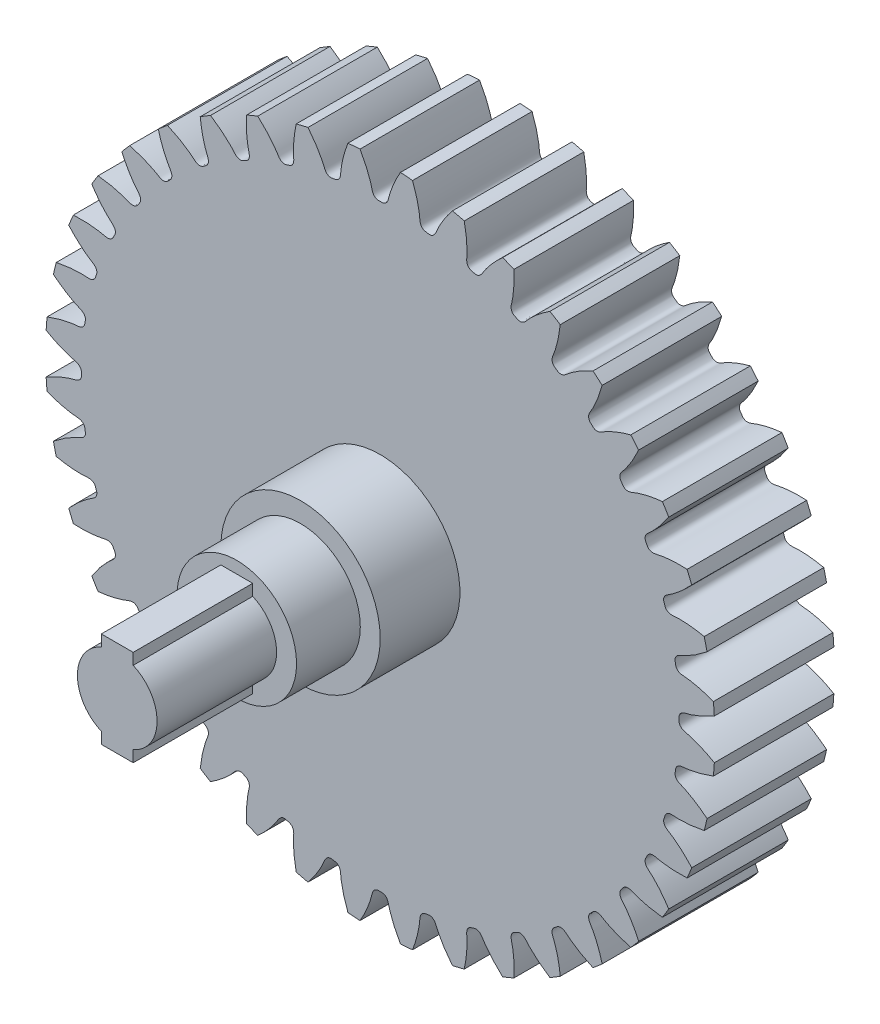
SolidWorks part; units mm, degrees
ref_plane "Front Plane" through (0, 0, 0) normal (0, 0, 1) x (1, 0, 0)
ref_plane "Top Plane" through (0, 0, 0) normal (0, 1, 0) x (1, 0, 0)
ref_plane "Right Plane" through (0, 0, 0) normal (1, 0, 0) x (0, 0, -1)
ref_axis "Axis1" through (0, 0, 55) along (0, 0, -1)
sketch "旋转草图小直齿轮" plane through (0, 0, 0) normal (1, 0, 0) x (0, 0, -1)
  line L0 (0, 0) -> (1, 0) construction
  line L1 (-7.5, 0) -> (-7.5, 42)
  line L2 (-7.5, 42) -> (7.5, 42)
  line L3 (7.5, 42) -> (7.5, 0)
  line L4 (7.5, 0) -> (-7.5, 0)
  dimension "Side1" = 7.5
  dimension "OutsideRadius" = 42
  dimension "Side2" = 7.5
revolve "小直齿轮" add sketch "旋转草图小直齿轮" angle 360 about L0
sketch "齿草图小直齿轮" plane through (0, 0, 0) normal (0, 0, 1) x (1, 0, 0)
  arc A0 (42.0201, 2.5926) -> (42.0201, -2.5926) centre (0, 0) cw
  spline S0 degree 3 poles (42.0201, -2.5926) (41.745, -2.4319) (41.3797, -2.2305) (40.9231, -2.0003) (40.668, -1.8774) (40.4215, -1.7639) (40.1839, -1.6595) (39.9554, -1.564) (39.7362, -1.4769) (39.5266, -1.3979) (39.3268, -1.3265) (39.1369, -1.2625) (38.9572, -1.2055) (38.7879, -1.155) (38.629, -1.1109) (38.4345, -1.0595) (38.2747, -1.0262) (38.152, -0.9881) (38.1049, -0.9719) (38.0584, -0.9542) (38.0124, -0.9347) (37.9666, -0.9132) (37.9208, -0.8892) (37.8747, -0.8622) (37.8283, -0.8314) (37.7813, -0.796) (37.7338, -0.7549) (37.6862, -0.7065) (37.6393, -0.6494) (37.5946, -0.5822) (37.5547, -0.5038) (37.523, -0.4143) (37.5038, -0.3202) (37.496, -0.1809) (37.5029, 0) (37.496, 0.1809) (37.5038, 0.3202) (37.523, 0.4143) (37.5547, 0.5038) (37.5946, 0.5822) (37.6393, 0.6494) (37.6862, 0.7065) (37.7338, 0.7549) (37.7813, 0.796) (37.8283, 0.8314) (37.8747, 0.8622) (37.9208, 0.8892) (37.9666, 0.9132) (38.0124, 0.9347) (38.0584, 0.9542) (38.1049, 0.9719) (38.152, 0.9881) (38.2747, 1.0262) (38.4345, 1.0595) (38.629, 1.1109) (38.7879, 1.155) (38.9572, 1.2055) (39.1369, 1.2625) (39.3268, 1.3265) (39.5266, 1.3979) (39.7362, 1.4769) (39.9554, 1.564) (40.1839, 1.6595) (40.4215, 1.7639) (40.668, 1.8774) (40.9231, 2.0003) (41.3797, 2.2305) (41.745, 2.4319) (42.0201, 2.5926) knots 0 0 0 0 0.086797 0.113582 0.139293 0.16393 0.187494 0.209983 0.231398 0.251739 0.271005 0.289198 0.306317 0.322362 0.337333 0.35123 0.377176 0.381719 0.386231 0.390736 0.395262 0.399843 0.40452 0.409344 0.414375 0.419685 0.425355 0.431479 0.438151 0.445453 0.45343 0.462059 0.471223 0.479506 0.5 0.520494 0.528777 0.537941 0.54657 0.554547 0.561849 0.568521 0.574645 0.580315 0.585625 0.590656 0.59548 0.600157 0.604738 0.609264 0.613769 0.618281 0.622824 0.64877 0.662667 0.677638 0.693683 0.710802 0.728995 0.748261 0.768602 0.790017 0.812506 0.83607 0.860707 0.886418 0.913203 1 1 1 1
extrude "齿拉伸切除小直齿轮" cut sketch "齿草图小直齿轮" against normal blind 7.5 and the other way blind 7.5
pattern_circular "齿形小直齿轮" count 40 every 9 about axis through (0, 0, 55) along (0, 0, -1) of "齿拉伸切除小直齿轮"
sketch "辅助草图小直齿轮" plane through (0, 0, 0) normal (0, 0, 1) x (1, 0, 0)
  circle A0 centre (0, 0) radius 40 construction
  circle A1 centre (0, 0) radius 37.5877 construction
  circle A2 centre (0, 0) radius 38.3337 construction
  circle A3 centre (0, 0) radius 42 construction
  circle A4 centre (0, 0) radius 37.5 construction
  dimension "PitchDiameter" = 80
  dimension "BaseDiameter" = 75.1754
  dimension "FormDiameter" = 76.6673
  dimension "MajorDiameter" = 84
  dimension "MinorDiameter" = 75
sketch "Sketch5" plane through (0, 0, 7.5) normal (0, 0, 1) x (1, 0, 0)
  circle A0 centre (0, 0) radius 10
  dimension "D1" = 20
extrude "Extrude2" add sketch "Sketch5" along normal blind 10
sketch "Sketch6" plane through (0, 0, 17.5) normal (0, 0, 1) x (1, 0, 0)
  circle A1 centre (0, 0) radius 7.5
  dimension "D1" = 15
extrude "Extrude3" add sketch "Sketch6" along normal blind 8
sketch "Sketch7" plane through (0, 0, 25.5) normal (0, 0, 1) x (1, 0, 0)
  circle A0 centre (0, 0) radius 5
  dimension "D1" = 10
extrude "Extrude4" add sketch "Sketch7" along normal blind 15
sketch "Sketch8" plane through (0, 0, 40.5) normal (0, 0, 1) x (1, 0, 0)
  line L0 (0, 0) -> (-5, 0)
  circle A0 centre (0, 0) radius 5 construction
sketch "Sketch9" plane through (0, 0, 40.5) normal (0, 0, 1) x (1, 0, 0)
  line L1 (-2, 6) -> (2, 6)
  line L2 (-2, 6) -> (-2, -6)
  line L3 (-2, -6) -> (2, -6)
  line L4 (2, 6) -> (2, -6)
  line L5 (-2, 6) -> (2, -6) construction
  line L6 (-2, -6) -> (2, 6) construction
  circle A0 centre (0, 0) radius 5 construction
  point P0 (0, 0)
  dimension "D2" = 6
  dimension "D1" = 4
extrude "Extrude5" add sketch "Sketch9" against normal up to surface (15 mm away) up to face at (5, 0, 25.5)
